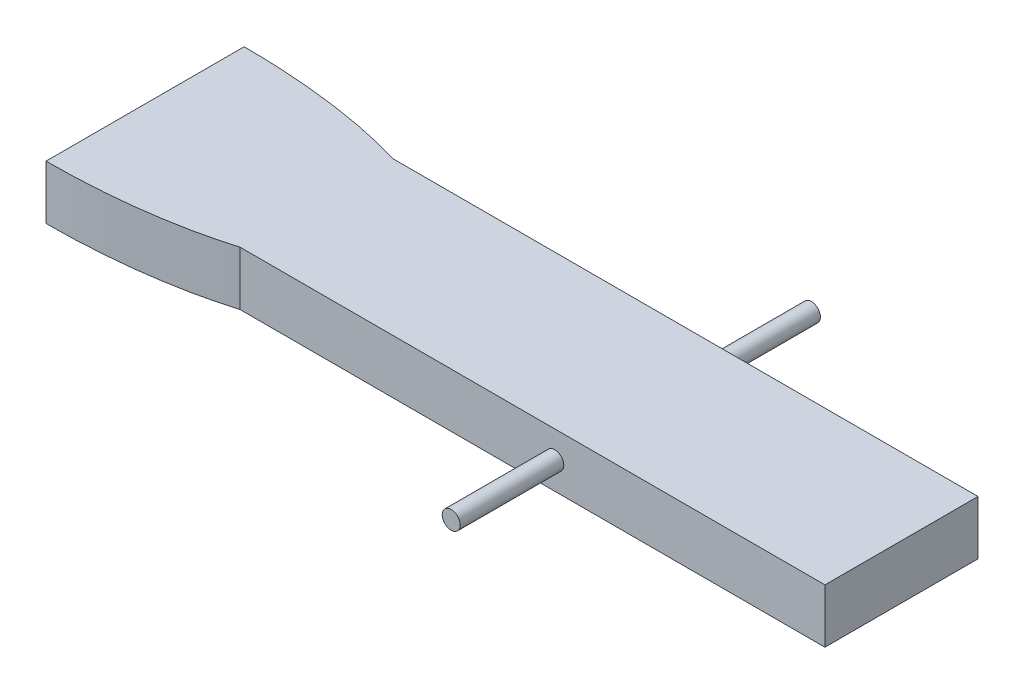
SolidWorks part; units mm, degrees
material "Stainless Steel (ferritic)"
ref_plane "Front Plane" through (0, 0, 0) normal (0, 0, 1) x (1, 0, 0)
ref_plane "Top Plane" through (0, 0, 0) normal (0, 1, 0) x (1, 0, 0)
ref_plane "Right Plane" through (0, 0, 0) normal (1, 0, 0) x (0, 0, -1)
sketch "Sketch1" plane through (0, 0, 0) normal (0, 0, 1) x (1, 0, 0)
  line L0 (0, 0) -> (-27, 0) construction
  line L1 (-27, -1.5) -> (-27, 1.5)
  line L2 (-27, 1.5) -> (15, 1.5)
  line L3 (-27, -1.5) -> (15, -1.5)
  line L4 (15, -1.5) -> (15, 1.5)
  circle A0 centre (0, 0) radius 0.75 construction
  point P9 (-27, 0)
  dimension "D1" = 1.5
  dimension "D2" = 27
  dimension "D3" = 3
  dimension "D4" = 15
extrude "Boss-Extrude1" add sketch "Sketch1" against normal blind 5.5 and the other way blind 5.5
sketch "Sketch2" plane through (0, 1.5, 0) normal (0, 1, 0) x (1, 0, 0)
  line L0 (15, -4.25) -> (15, 4.25)
  line L1 (-27, -5.5) -> (-27, 5.5) construction
  line L2 (-12, 0) -> (15, 0) construction
  line L3 (15, -5.5) -> (15, 5.5) construction
  line L4 (15, 4.25) -> (-17.4789, 4.25)
  line L5 (15, -4.25) -> (-17.4789, -4.25)
  line L6 (-27, 5.5) -> (-27, -5.5)
  ellipse E0 centre (-27, 0) end of major axis (-12, 0) minor radius 5.5 (-27, 5.5) -> (-27, -5.5) cw construction
  ellipse E1 centre (-27, 0) end of major axis (-12, 0) minor radius 5.5 (-27, 5.5) -> (-17.4789, 4.25) cw
  ellipse E2 centre (-27, 0) end of major axis (-12, 0) minor radius 5.5 (-27, -5.5) -> (-17.4789, -4.25) ccw
  point P18 (15, 0)
  dimension "D1" = 15
  dimension "D2" = 8.5
extrude "Cut-Extrude1" cut sketch "Sketch2" against normal through all flip side to cut
sketch "Sketch3" plane through (0, 0, 0) normal (0, 0, 1) x (1, 0, 0)
  circle A0 centre (0, 0) radius 0.5
  dimension "D1" = 1
extrude "Boss-Extrude2" add sketch "Sketch3" along normal blind 10 and the other way blind 10
